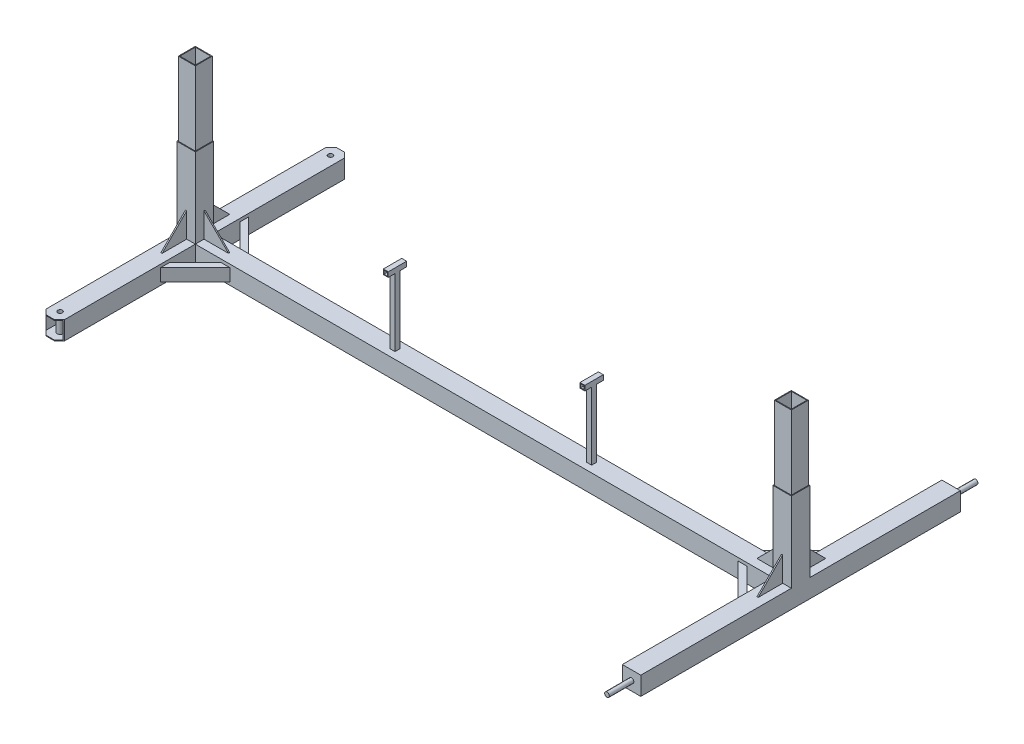
SolidWorks part; units mm, degrees
material "Plain Carbon Steel"
ref_plane "Front Plane" through (0, 0, 0) normal (0, 0, 1) x (1, 0, 0)
ref_plane "Top Plane" through (0, 0, 0) normal (0, 1, 0) x (1, 0, 0)
ref_plane "Right Plane" through (0, 0, 0) normal (1, 0, 0) x (0, 0, -1)
sketch "Sketch1" plane through (0, 0, 0) normal (0, 1, 0) x (1, 0, 0)
  line L0 (0, 600) -> (0, 0) construction
  line L1 (-1250, 600) -> (1250, 600) construction
  line L2 (-1250, 600) -> (-1250, -600) construction
  line L3 (-1250, -600) -> (1250, -600) construction
  line L4 (0, 0) -> (0, -600) construction
  line L5 (1250, 600) -> (1250, -600) construction
  line L7 (1250, 600) -> (1250, -600) construction
  dimension "D1" = 1200
  dimension "D2" = 2500
sketch "Sketch24" plane through (0, 0, 0) normal (0, 1, 0) x (1, 0, 0)
  line L0 (-1250, 600) -> (-1250, -600) construction
  line L1 (-1250, -37.5) -> (1250, -37.5)
  line L2 (-1250, -37.5) -> (-1250, 37.5)
  line L3 (-1250, 37.5) -> (1250, 37.5)
  line L4 (1250, -37.5) -> (1250, 37.5)
  line L5 (1250, 600) -> (1250, -600) construction
  line L6 (-1250, 0) -> (0, 0) construction
  line L7 (0, 0) -> (1250, 0) construction
  dimension "D1" = 75
extrude "Boss-Extrude19" add sketch "Sketch24" along normal blind 75
sketch "Sketch25" plane through (0, 75, 0) normal (0, 1, 0) x (1, 0, 0)
  line L0 (1250, 37.5) -> (-1250, 37.5) construction
  line L1 (-1250, -37.5) -> (-1175, -37.5)
  line L2 (-1250, -37.5) -> (-1250, 37.5)
  line L3 (-1250, 37.5) -> (-1175, 37.5)
  line L4 (-1175, -37.5) -> (-1175, 37.5)
  line L6 (1250, -37.5) -> (1175, -37.5)
  line L7 (1250, -37.5) -> (1250, 37.5)
  line L8 (1250, 37.5) -> (1175, 37.5)
  line L9 (1175, -37.5) -> (1175, 37.5)
extrude "Boss-Extrude21" add sketch "Sketch25" along normal blind 325
sketch "Sketch27" plane through (0, 400, 0) normal (0, 1, 0) x (1, 0, 0)
  line L14 (-1247, 34.5) -> (-1247, -34.5)
  line L15 (-1247, -34.5) -> (-1178, -34.5)
  line L16 (-1178, -34.5) -> (-1178, 34.5)
  line L17 (-1178, 34.5) -> (-1247, 34.5)
  line L18 (-1247, 34.5) -> (-1247, -34.5)
  line L19 (-1247, -34.5) -> (-1178, -34.5)
  line L20 (-1178, -34.5) -> (-1178, 34.5)
  line L21 (-1178, 34.5) -> (-1247, 34.5)
  line L36 (1247, -34.5) -> (1247, 34.5)
  line L37 (1178, -34.5) -> (1247, -34.5)
  line L38 (1178, 34.5) -> (1178, -34.5)
  line L39 (1247, 34.5) -> (1178, 34.5)
  line L40 (1247, -34.5) -> (1247, 34.5)
  line L41 (1178, -34.5) -> (1247, -34.5)
  line L42 (1178, 34.5) -> (1178, -34.5)
  line L43 (1247, 34.5) -> (1178, 34.5)
  dimension "D1" = 3
  dimension "D2" = 3
extrude "Boss-Extrude22" add sketch "Sketch27" along normal blind 300
sketch "Sketch36" plane through (0, 75, 0) normal (0, 1, 0) x (1, 0, 0)
  line L0 (-390, 0) -> (0, 0) construction
  line L1 (-410, 10) -> (-390, 10)
  line L2 (-410, 10) -> (-410, -10)
  line L3 (-410, -10) -> (-390, -10)
  line L4 (-390, 10) -> (-390, -10)
  dimension "D1" = 20
  dimension "D2" = 390
extrude "Boss-Extrude29" add sketch "Sketch36" along normal blind 275
sketch "Sketch37" plane through (0, 0, 0) normal (0, 0, 1) x (1, 0, 0)
  line L1 (-410, 350) -> (-390, 350)
  line L2 (-410, 350) -> (-410, 370)
  line L3 (-410, 370) -> (-390, 370)
  line L4 (-390, 350) -> (-390, 370)
extrude "Boss-Extrude30" add sketch "Sketch37" along normal mid plane 75
sketch "Sketch44" plane through (0, 0, 0) normal (0, 0, 1) x (1, 0, 0)
  line L1 (-1250, 0) -> (-1175, 0)
  line L2 (-1250, 0) -> (-1250, 75)
  line L3 (-1250, 75) -> (-1175, 75)
  line L4 (-1175, 0) -> (-1175, 75)
extrude "Boss-Extrude35" add sketch "Sketch44" along normal mid plane 1180
sketch "Sketch46" plane through (0, 0, 0) normal (0, 0, 1) x (1, 0, 0)
  line L1 (1250, 0) -> (1175, 0)
  line L2 (1250, 0) -> (1250, 75)
  line L3 (1250, 75) -> (1175, 75)
  line L4 (1175, 0) -> (1175, 75)
extrude "Boss-Extrude36" add sketch "Sketch46" along normal mid plane 1300
ref_plane "Plane1" through (0, 37.5, 0) normal (0, 1, 0) x (1, 0, 0)
sketch "Sketch47" plane through (0, 37.5, 0) normal (0, 1, 0) x (1, 0, 0)
  line L0 (-1175, 178.9214) -> (-1175, 143.566)
  line L1 (-1175, 37.5) -> (-1175, 590) construction
  line L2 (-1175, 143.566) -> (-1068.934, 37.5)
  line L3 (1175, 37.5) -> (-1175, 37.5) construction
  line L4 (-1068.934, 37.5) -> (-1033.5786, 37.5)
  line L5 (-1033.5786, 37.5) -> (-1175, 178.9214)
  line L6 (-1175, -143.566) -> (-1068.934, -37.5)
  line L7 (-1175, -590) -> (-1175, -37.5) construction
  line L8 (-1175, -37.5) -> (1175, -37.5) construction
  line L9 (-1068.934, -37.5) -> (-1033.5786, -37.5)
  line L10 (-1033.5786, -37.5) -> (-1175, -178.9214)
  line L11 (-1175, -178.9214) -> (-1175, -143.566)
  dimension "D1" = 25
  dimension "D2" = 200
extrude "Boss-Extrude37" add sketch "Sketch47" along normal mid plane 50
mirror "Mirror4" about plane through (0, 0, 0) normal (1, 0, 0) of "Boss-Extrude37"
other "Gusset1" parameters "D1"=5, "D2"=5, "D3"=0, "D4"=0, "D10"=5, "D11"=100, "D12"=100, "D13"=15, "D14"=45, "D15"=15, "D16"=50, "D17"=50, "D18"=45
sketch "Sketch48" plane through (-1212.5, 75, 37.5) normal (-1, 0, 0) x (0, 0, 1)
  line L0 (0, 0) -> (100, 0)
  line L1 (0, 0) -> (0, 100)
  line L2 (100, 0) -> (0, 100)
other "Gusset2" parameters "D1"=5, "D2"=5, "D3"=0, "D4"=0, "D10"=5, "D11"=100, "D12"=100, "D13"=15, "D14"=45, "D15"=15
sketch "Sketch49" plane through (-1175, 75, 0) normal (0, 0, -1) x (-1, 0, 0)
  line L0 (0, 0) -> (0, 100)
  line L1 (0, 0) -> (-100, 0)
  line L2 (0, 100) -> (-100, 0)
other "Gusset3" parameters "D1"=5, "D2"=5, "D3"=0, "D4"=0, "D10"=5, "D11"=100, "D12"=100, "D13"=15, "D14"=45, "D15"=15
sketch "Sketch50" plane through (-1212.5, 75, -37.5) normal (-1, 0, 0) x (0, 0, 1)
  line L0 (0, 0) -> (0, 100)
  line L1 (0, 0) -> (-100, 0)
  line L2 (0, 100) -> (-100, 0)
other "Gusset4" parameters "D1"=5, "D2"=5, "D3"=0, "D4"=0, "D10"=5, "D11"=100, "D12"=100, "D13"=15, "D14"=45, "D15"=15
sketch "Sketch51" plane through (1212.5, 75, -37.5) normal (1, 0, 0) x (0, 0, -1)
  line L0 (0, 0) -> (100, 0)
  line L1 (0, 0) -> (0, 100)
  line L2 (100, 0) -> (0, 100)
other "Gusset5" parameters "D1"=5, "D2"=5, "D3"=0, "D4"=0, "D10"=5, "D11"=100, "D12"=100, "D13"=15, "D14"=45, "D15"=15
sketch "Sketch52" plane through (1212.5, 75, 37.5) normal (-1, 0, 0) x (0, 0, 1)
  line L0 (0, 0) -> (100, 0)
  line L1 (0, 0) -> (0, 100)
  line L2 (100, 0) -> (0, 100)
other "Gusset6" parameters "D1"=5, "D2"=5, "D3"=0, "D4"=0, "D10"=5, "D11"=100, "D12"=100, "D13"=15, "D14"=45, "D15"=15
sketch "Sketch53" plane through (1175, 75, 0) normal (0, 0, -1) x (-1, 0, 0)
  line L0 (0, 0) -> (100, 0)
  line L1 (0, 0) -> (0, 100)
  line L2 (100, 0) -> (0, 100)
mirror "Mirror5" about plane through (0, 0, 0) normal (1, 0, 0) of "Boss-Extrude30", "Boss-Extrude29"
shell "Shell7" thickness 3
sketch "Sketch54" plane through (0, 75, 0) normal (0, 1, 0) x (1, 0, 0)
  line L0 (-1212.5, -550) -> (-1212.5, 0) construction
  line L1 (-1212.5, 0) -> (-1212.5, 550) construction
  line L2 (-1212.5, 0) -> (0, 0) construction
  circle A0 centre (-1212.5, 550) radius 12.5
  circle A1 centre (-1212.5, -550) radius 12.5
  point P4 (-1209.3764, 0)
  dimension "D3" = 25
  dimension "D1" = 1212.5
  dimension "D2" = 1100
extrude "Boss-Extrude38" add sketch "Sketch54" against normal up to surface (75 mm away) up to face at (0, 0, 0)
sketch "Sketch55" plane through (0, 75, 0) normal (0, 1, 0) x (1, 0, 0)
  circle A0 centre (-1212.5, 550) radius 9.5
  circle A1 centre (-1212.5, -550) radius 9.5
  dimension "D1" = 19
extrude "Cut-Extrude1" cut sketch "Sketch55" against normal through all
chamfer "Chamfer1" distance 20 angle 45 4 edges at (-1250, 37.5, -590) (-1175, 37.5, -590) (-1250, 37.5, 590) (-1175, 37.5, 590)
sketch "Sketch56" plane through (0, 0, 0) normal (0, -1, 0) x (1, 0, 0)
  line L0 (-1250, 50) -> (-1175, 50)
  line L1 (-1250, -570) -> (-1250, 570) construction
  line L2 (-1175, 570) -> (-1175, 37.5) construction
  line L3 (-1175, 50) -> (-1150, 37.5)
  line L4 (-1175, 37.5) -> (1175, 37.5) construction
  line L5 (-1150, 37.5) -> (-1150, -37.5)
  line L6 (1175, -37.5) -> (-1175, -37.5) construction
  line L7 (-1150, -37.5) -> (-1175, -50)
  line L8 (-1175, -37.5) -> (-1175, -570) construction
  line L9 (-1175, -50) -> (-1250, -50)
  line L10 (-1250, -50) -> (-1250, 50)
  point P6 (-1160.5407, 37.5)
  dimension "D1" = 100
  dimension "D2" = 100
extrude "Boss-Extrude39" add sketch "Sketch56" along normal blind 6 separate body
sketch "Sketch57" plane through (0, -6, 0) normal (0, -1, 0) x (1, 0, 0)
  line L0 (-1212.5, 0) -> (-1250, 0) construction
  line L1 (-1250, -570) -> (-1250, 570) construction
  line L2 (-1250, 50) -> (-1250, -50) construction
  line L3 (-1175, -37.5) -> (-1175, -570) construction
  line L4 (-1175, 0) -> (-1212.5, 0) construction
  circle A0 centre (-1212.5, 0) radius 9.5
  point P2 (-1212.5, -0.1167)
  dimension "D1" = 19
extrude "Boss-Extrude40" add sketch "Sketch57" along normal blind 30 separate body
sketch "Sketch59" plane through (0, 0, 650) normal (0, 0, 1) x (1, 0, 0)
  line L1 (1175, 75) -> (1250, 75)
  line L2 (1175, 75) -> (1175, 0)
  line L3 (1175, 0) -> (1250, 0)
  line L4 (1250, 75) -> (1250, 0)
extrude "Boss-Extrude41" add sketch "Sketch59" against normal blind 8
sketch "Sketch60" plane through (0, 0, 650) normal (0, 0, 1) x (1, 0, 0)
  line L0 (1212.5, 75) -> (1212.5, 37.5) construction
  line L1 (1250, 75) -> (1175, 75) construction
  line L2 (1212.5, 37.5) -> (1212.5, 0) construction
  line L3 (1175, 0) -> (1250, 0) construction
  circle A0 centre (1212.5, 37.5) radius 9.5
  dimension "D1" = 19
extrude "Boss-Extrude42" add sketch "Sketch60" along normal blind 100
mirror "Mirror9" about plane through (0, 0, 0) normal (0, 0, 1) of "Boss-Extrude42", "Boss-Extrude41"
